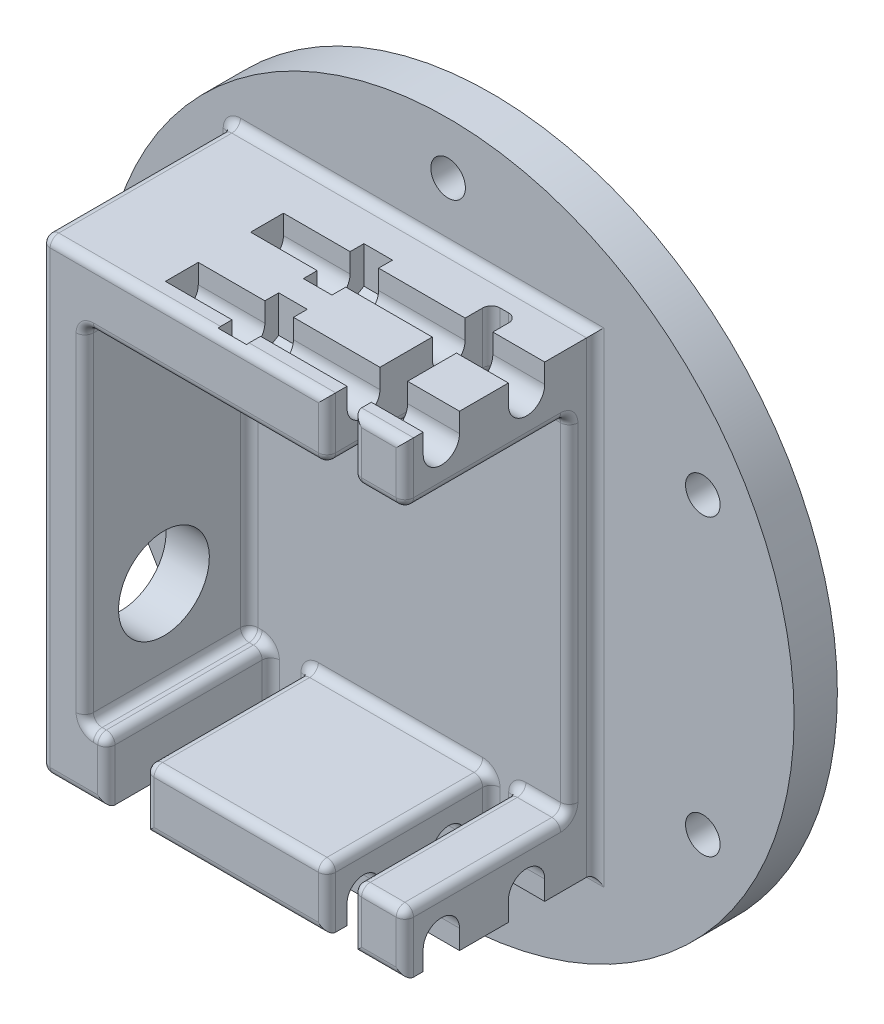
SolidWorks part; units mm, degrees
ref_plane "Plano frontal" through (0, 0, 0) normal (0, 0, 1) x (1, 0, 0)
ref_plane "Plano superior" through (0, 0, 0) normal (0, 1, 0) x (1, 0, 0)
ref_plane "Plano direito" through (0, 0, 0) normal (1, 0, 0) x (0, 0, -1)
sketch "Esboço1" plane through (0, 0, 0) normal (0, 0, 1) x (1, 0, 0)
  circle A0 centre (0, 0) radius 40
  circle A1 centre (0, 34) radius 2
  circle A2 centre (29.4449, 17) radius 2
  circle A3 centre (29.4449, -17) radius 2
  circle A4 centre (0, -34) radius 2
  circle A5 centre (-29.4449, -17) radius 2
  circle A6 centre (-29.4449, 17) radius 2
  point P18 (0, 0)
  dimension "D1" = 80
  dimension "D3" = 4
  dimension "D4" = 34
  dimension "D2" = 6
extrude "Ressalto-extrusão1" add sketch "Esboço1" along normal blind 5
ref_plane "Plano2" through (0, 0, 8) normal (0, 0, 1) x (1, 0, 0)
sketch "Esboço2" plane through (0, 0, 8) normal (0, 0, 1) x (1, 0, 0)
  line L0 (-17.5, 27) -> (-13, 27)
  line L1 (-20, 20) -> (17, 20) construction
  line L2 (-20, 20) -> (-20, -20) construction
  line L3 (-20, -20) -> (20, -20) construction
  line L4 (20, 0) -> (20, -20) construction
  line L5 (-20, 20) -> (20, -20) construction
  line L6 (-20, -20) -> (20, 20) construction
  line L7 (20, 0) -> (-20, 0) construction
  line L8 (-13, 27) -> (8, 27)
  line L10 (-13, 20) -> (8, 20)
  line L11 (8, 27) -> (8, 20)
  line L12 (-13, 27) -> (8, 20) construction
  line L13 (-13, 20) -> (8, 27) construction
  line L15 (-20, 20) -> (-20, -20)
  line L17 (-25, 20) -> (-25, -20)
  line L18 (-20, 20) -> (-17.5, 20)
  line L19 (-25, 20) -> (-25, 27)
  line L20 (-25, 27) -> (-17.5, 27)
  line L22 (8, -27) -> (8, -20)
  line L23 (-13, -27) -> (8, -27)
  line L24 (-13, -27) -> (-13, -20)
  line L25 (-13, -20) -> (8, -20)
  line L26 (-20, -20) -> (-17.5, -20)
  line L27 (-17.5, -20) -> (-17.5, -27)
  line L28 (-25, -27) -> (-17.5, -27)
  line L29 (-25, -20) -> (-25, -27)
  line L30 (-17.5, 20) -> (-13, 20)
  line L31 (17, 20) -> (17, 27)
  line L32 (11, 20) -> (17, 20)
  line L33 (11, 20) -> (11, 27)
  line L34 (11, 27) -> (17, 27)
  line L40 (11, -20) -> (17, -20)
  line L41 (11, -20) -> (11, -27)
  line L42 (11, -27) -> (17, -27)
  line L43 (17, -20) -> (17, -27)
  line L44 (19.5, 20) -> (20, 20) construction
  line L45 (20, 0) -> (20, 20) construction
  line L46 (17, 20) -> (19.5, 20) construction
  point P0 (0, 0)
  point P10 (-2.5, 23.5)
  dimension "D1" = 40
  dimension "D2" = 40
  dimension "D3" = 21
  dimension "D4" = 7
  dimension "D5" = 5
  dimension "D6" = 2.5
  dimension "D7" = 7
  dimension "D8" = 40
  dimension "D9" = 4.5
  dimension "D10" = 3
  dimension "D11" = 6
  dimension "D13" = 7
  dimension "D14" = 7
  dimension "D17" = 6
extrude "Ressalto-extrusão2" add sketch "Esboço2" along normal blind 19
sketch "Esboço3" plane through (17, 0, 0) normal (1, 0, 0) x (0, 0, -1)
  line L0 (0, 0) -> (-27, 0) construction
  line L1 (-27, -20) -> (-27, 20) construction
  line L2 (-24, -24.76) -> (-5, -24.76) construction
  line L3 (-10.83, 27) -> (-15.03, 27)
  line L5 (-27, -20) -> (-8, -20) construction
  line L6 (-24.88, -24.76) -> (-24.88, -27)
  line L7 (-27, -27) -> (-8, -27) construction
  line L8 (-20.68, -24.76) -> (-20.68, -27)
  line L9 (-20.68, -27) -> (-24.88, -27)
  line L10 (-15.03, -24.76) -> (-15.03, -27)
  line L11 (-10.83, -24.76) -> (-10.83, -27)
  line L12 (-10.83, -27) -> (-15.03, -27)
  line L13 (-10.83, 24.76) -> (-10.83, 27)
  line L14 (-15.03, 24.76) -> (-15.03, 27)
  line L15 (-20.68, 27) -> (-24.88, 27)
  line L16 (-20.68, 24.76) -> (-20.68, 27)
  line L17 (-24.88, 24.76) -> (-24.88, 27)
  line L18 (-8, 44) -> (-8, -44) construction
  arc A0 (-20.68, -24.76) -> (-24.88, -24.76) centre (-22.78, -24.76) ccw
  arc A1 (-10.83, -24.76) -> (-15.03, -24.76) centre (-12.93, -24.76) ccw
  arc A2 (-10.83, 24.76) -> (-15.03, 24.76) centre (-12.93, 24.76) cw
  arc A3 (-20.68, 24.76) -> (-24.88, 24.76) centre (-22.78, 24.76) cw
  dimension "D1" = 4.2
  dimension "D2" = 9.85
  dimension "D3" = 4.93
  dimension "D4" = 4.76
extrude "Corte-extrusão1" cut sketch "Esboço3" against normal up to surface (9 mm away) up to face at (8, 23.5, 17.5)
sketch "Esboço4" plane through (8, 0, 0) normal (1, 0, 0) x (0, 0, -1)
  line L1 (-24.68, -24.76) -> (-24.68, -27)
  line L2 (-27, -27) -> (-8, -27) construction
  line L3 (-20.88, -24.76) -> (-20.88, -27)
  line L4 (-20.88, -27) -> (-24.68, -27)
  line L5 (-14.83, -24.76) -> (-14.83, -27)
  line L6 (-11.03, -24.76) -> (-11.03, -27)
  line L7 (-14.83, -27) -> (-11.03, -27)
  line L8 (14.85, 0) -> (-14.85, 0) construction
  line L9 (-14.83, 27) -> (-11.03, 27)
  line L10 (-11.03, 24.76) -> (-11.03, 27)
  line L11 (-14.83, 24.76) -> (-14.83, 27)
  line L12 (-20.88, 27) -> (-24.68, 27)
  line L13 (-20.88, 24.76) -> (-20.88, 27)
  line L14 (-24.68, 24.76) -> (-24.68, 27)
  arc A0 (-20.88, -24.76) -> (-24.68, -24.76) centre (-22.78, -24.76) ccw
  arc A1 (-11.03, -24.76) -> (-14.83, -24.76) centre (-12.93, -24.76) ccw
  arc A4 (-11.03, 24.76) -> (-14.83, 24.76) centre (-12.93, 24.76) cw
  arc A5 (-20.88, 24.76) -> (-24.68, 24.76) centre (-22.78, 24.76) cw
  dimension "D1" = 3.8
sketch "Esboço7" plane through (0, 0, 5) normal (0, 0, 1) x (1, 0, 0)
  line L1 (-25, 27) -> (17, 27)
  line L2 (-25, 27) -> (-25, -27)
  line L3 (-25, -27) -> (17, -27)
  line L4 (17, 27) -> (17, -27)
extrude "Ressalto-extrusão4" add sketch "Esboço7" along normal blind 3
extrude "Corte-extrusão2" cut sketch "Esboço4" against normal up to surface (21 mm away) up to face at (-13, -23.5, 17.5)
ref_plane "Plano1" through (-2, 0, 0) normal (1, 0, 0) x (0, 0, -1)
sketch "Esboço5" plane through (-2, 0, 0) normal (1, 0, 0) x (0, 0, -1)
  line L0 (-20.88, 24.76) -> (-20.88, 27) construction
  line L1 (-19.28, 22.7393) -> (-19.28, 26.7807)
  line L4 (-26.28, 26.7807) -> (-26.28, 22.7393)
  line L5 (-26.28, 22.7393) -> (-22.78, 20.7185)
  line L6 (-22.78, 20.7185) -> (-19.28, 22.7393)
  line L7 (-26.28, 26.7807) -> (-26.28, 27)
  line L8 (-27, 27) -> (-24.88, 27) construction
  line L9 (-26.28, 27) -> (-19.28, 27)
  line L10 (-20.68, 27) -> (-15.03, 27) construction
  line L11 (-19.28, 27) -> (-19.28, 26.7807)
  line L12 (-17.855, 27) -> (-17.855, -27) construction
  line L13 (-25.9002, 27) -> (-26.132, 26.8662) [skipped]
  line L14 (-19.28, 26.7807) -> (-19.6598, 27) [skipped]
  line L15 (-20.68, -27) -> (-15.03, -27) construction
  line L16 (-16.43, 27) -> (-16.43, 26.7807)
  line L17 (-9.43, 27) -> (-16.43, 27)
  line L18 (-9.43, 26.7807) -> (-9.43, 27)
  line L19 (-12.93, 20.7185) -> (-16.43, 22.7393)
  line L20 (-9.43, 22.7393) -> (-12.93, 20.7185)
  line L21 (-9.43, 26.7807) -> (-9.43, 22.7393)
  line L22 (-16.43, 22.7393) -> (-16.43, 26.7807)
  line L23 (14.85, 0) -> (-14.85, 0) construction
  line L24 (-16.43, -22.7393) -> (-16.43, -26.7807)
  line L25 (-9.43, -26.7807) -> (-9.43, -22.7393)
  line L26 (-9.43, -22.7393) -> (-12.93, -20.7185)
  line L27 (-12.93, -20.7185) -> (-16.43, -22.7393)
  line L28 (-9.43, -26.7807) -> (-9.43, -27)
  line L29 (-9.43, -27) -> (-16.43, -27)
  line L30 (-16.43, -27) -> (-16.43, -26.7807)
  line L31 (-19.28, -27) -> (-19.28, -26.7807)
  line L32 (-26.28, -27) -> (-19.28, -27)
  line L33 (-26.28, -26.7807) -> (-26.28, -27)
  line L34 (-22.78, -20.7185) -> (-19.28, -22.7393)
  line L35 (-26.28, -22.7393) -> (-22.78, -20.7185)
  line L36 (-26.28, -26.7807) -> (-26.28, -22.7393)
  line L37 (-19.28, -22.7393) -> (-19.28, -26.7807)
  arc A0 (-25.4693, 27) -> (-20.0907, 27) centre (-22.78, 24.76) ccw construction
  arc A1 (-10.2407, 27) -> (-15.6193, 27) centre (-12.93, 24.76) cw construction
  arc A2 (-10.2407, -27) -> (-15.6193, -27) centre (-12.93, -24.76) ccw construction
  arc A3 (-25.4693, -27) -> (-20.0907, -27) centre (-22.78, -24.76) cw construction
  dimension "D1" = 7
extrude "Corte-extrusão3" cut sketch "Esboço5" against normal blind 3.3
fillet "Filete1" radius 1 23 edges at (17, 20, 17.5) (11, -23.5, 8) (8, -23.5, 8) (-13, -23.5, 8) (-17.5, -23.5, 8) (11, 23.5, 8) (8, 23.5, 8) (17, 0, 8) (11, -20, 17.5) (8, -20, 17.5) (-13, -20, 17.5) (-17.5, -20, 17.5) (11, 20, 17.5) (8, 20, 17.5) (17, -20, 17.5) (-20, -20, 17.5) (-20, 20, 17.5) (-20, 0, 8) (14, -20, 8) (-2.5, -20, 8) (-18.75, -20, 8) (-6, 20, 8) (14, 20, 8)
fillet "Filete2" radius 1 36 edges at (17, -24, 27) (16.7071, -20.2929, 27) (11, -24, 27) (11.2929, -20.2929, 27) (11, 24, 27) (11.2929, 20.2929, 27) (17, 24, 27) (16.7071, 20.2929, 27) (8, -24, 27) (7.7071, -20.2929, 27) (-13, -24, 27) (-12.7071, -20.2929, 27) (-17.5, -24, 27) (-17.7929, -20.2929, 27) (-18.75, -20, 27) (-19.7071, -19.7071, 27) (8, 24, 27) (7.7071, 20.2929, 27) (-6, 20, 27) (-19.7071, 19.7071, 27) (14, -20, 27) (14, 20, 27) (-2.5, -20, 27) (-20, 0, 27) (14, 27, 27) (14, -27, 27) (-2.5, -27, 27) (-8.5, 27, 27) (-25, 0, 27) (-21.25, -27, 27) (-25, -27, 16) (-25, 27, 16) (-25, 0, 5) (-4, 27, 5) (-4, -27, 5) (17, 0, 5)
sketch "Esboço8" plane through (-25, 0, 0) normal (-1, 0, 0) x (0, 0, 1)
  line L0 (6, -26) -> (26, -26) construction
  line L1 (6, 26) -> (6, -26) construction
  circle A0 centre (17.85, -10.15) radius 5.25
  dimension "D1" = 10.5
  dimension "D2" = 15.85
  dimension "D3" = 11.85
extrude "Corte-extrusão4" cut sketch "Esboço8" against normal up to surface (5 mm away) up to face at (-20, 0, 17.5)
